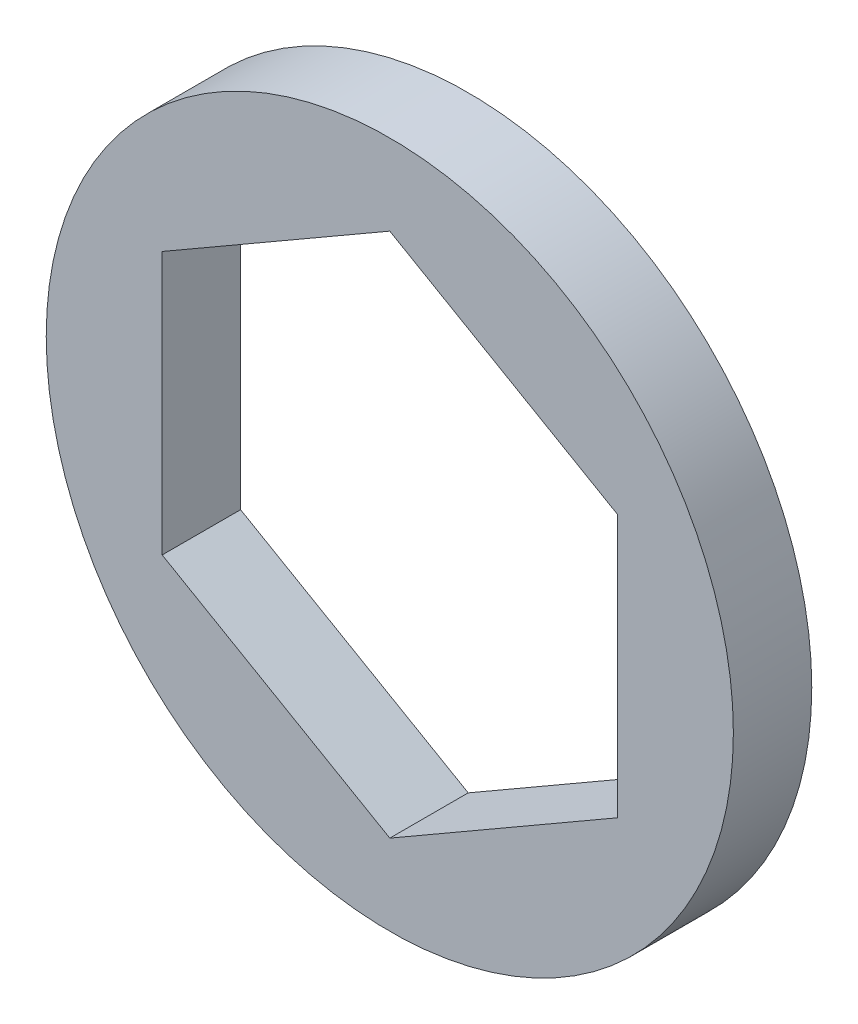
SolidWorks part; units mm, degrees
material "Nylon 101"
ref_plane "Front Plane" through (0, 0, 0) normal (0, 0, 1) x (1, 0, 0)
ref_plane "Top Plane" through (0, 0, 0) normal (0, 1, 0) x (1, 0, 0)
ref_plane "Right Plane" through (0, 0, 0) normal (1, 0, 0) x (0, 0, -1)
sketch "Sketch1" plane through (0, 0, 0) normal (0, 0, 1) x (1, 0, 0)
  line L1 (6.731, 3.8861) -> (0, 7.7723)
  line L2 (0, 7.7723) -> (-6.731, 3.8861)
  line L3 (-6.731, 3.8861) -> (-6.731, -3.8861)
  line L4 (-6.731, -3.8861) -> (0, -7.7723)
  line L5 (0, -7.7723) -> (6.731, -3.8861)
  line L6 (6.731, -3.8861) -> (6.731, 3.8861)
  circle A0 centre (0, 0) radius 6.731 construction
  circle A1 centre (0, 0) radius 10.16
  dimension "D1" = 13.462
  dimension "D2" = 20.32
extrude "Boss-Extrude1" add sketch "Sketch1" along normal blind 2.3185
